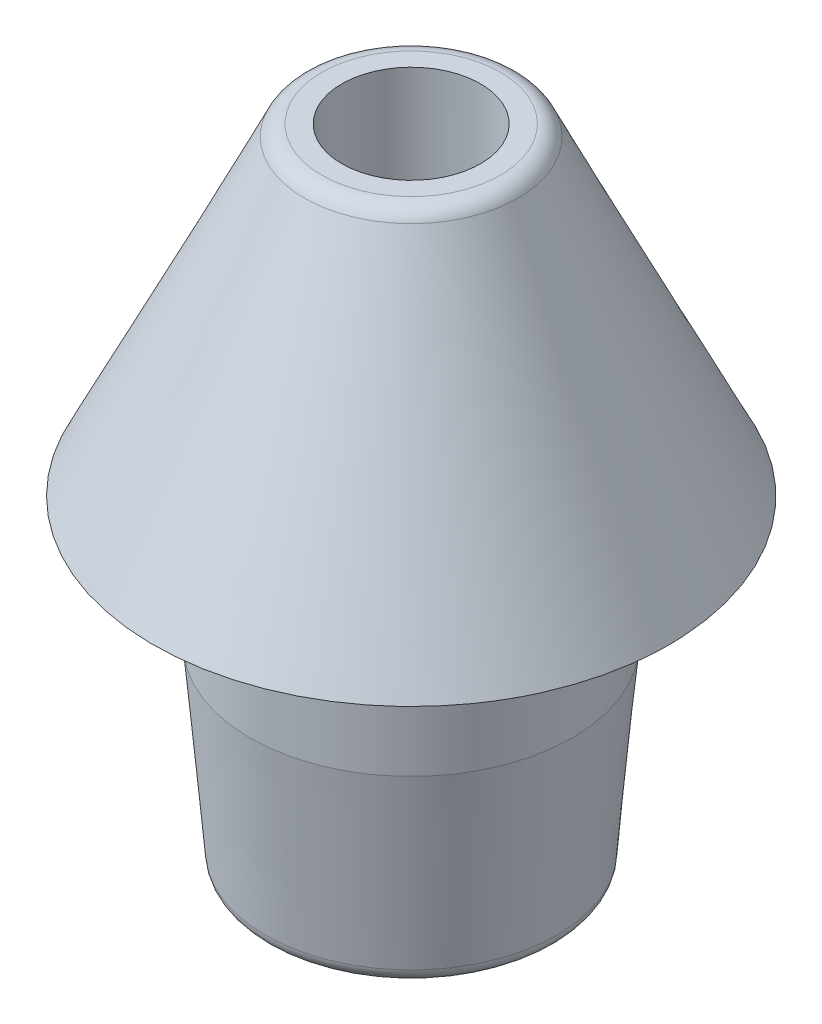
SolidWorks part; units mm, degrees
material "ABS"
ref_plane "Front Plane" through (0, 0, 0) normal (0, 0, 1) x (1, 0, 0)
ref_plane "Top Plane" through (0, 0, 0) normal (0, 1, 0) x (1, 0, 0)
ref_plane "Right Plane" through (0, 0, 0) normal (1, 0, 0) x (0, 0, -1)
sketch "Sketch1" plane through (0, 0, 0) normal (0, 1, 0) x (1, 0, 0)
  circle A0 centre (0, 0) radius 2.5
  dimension "D1" = 5
extrude "Boss-Extrude1" add sketch "Sketch1" along normal blind 5
sketch "Sketch2" plane through (0, 5, 0) normal (0, 1, 0) x (1, 0, 0)
  circle A0 centre (0, 0) radius 4
  dimension "D1" = 8
ref_plane "Plane1" through (0, 10, 0) normal (0, 1, 0) x (1, 0, 0)
sketch "Sketch3" plane through (0, 10, 0) normal (0, 1, 0) x (1, 0, 0)
  circle A0 centre (0, 0) radius 1.575
  circle A1 centre (0, 0) radius 1.075 construction
  dimension "D1" = 0.5
  dimension "D2" = 2.15
loft "Loft1" add profiles "Sketch3", "Sketch2" connector at (-1.3924, 10, -0.7361) connector at (-3.844, 5, -1.1063)
sketch "Sketch4" plane through (0, 10, 0) normal (0, 1, 0) x (1, 0, 0)
  circle A0 centre (0, 0) radius 1.075
  dimension "D1" = 2.15
extrude "Cut-Extrude1" cut sketch "Sketch4" against normal through all
chamfer "Chamfer1" distance 0.3 angle 87 1 edges at (0, 0, 1.075) first distance on face at (0, 0, 1.075)
chamfer "Chamfer2" distance 3 angle 5 1 edges at (0, 0, 2.5) first distance on face at (0, 5, 2.5)
fillet "Fillet1" radius 0.3 1 edges at (0, 10, 1.575)
fillet "Fillet2" radius 0.25 1 edges at (0, 5, 2.5)
fillet "Fillet4" radius 0.25 2 edges at (0, 0, 1.375) (0, 0, 2.2375)
